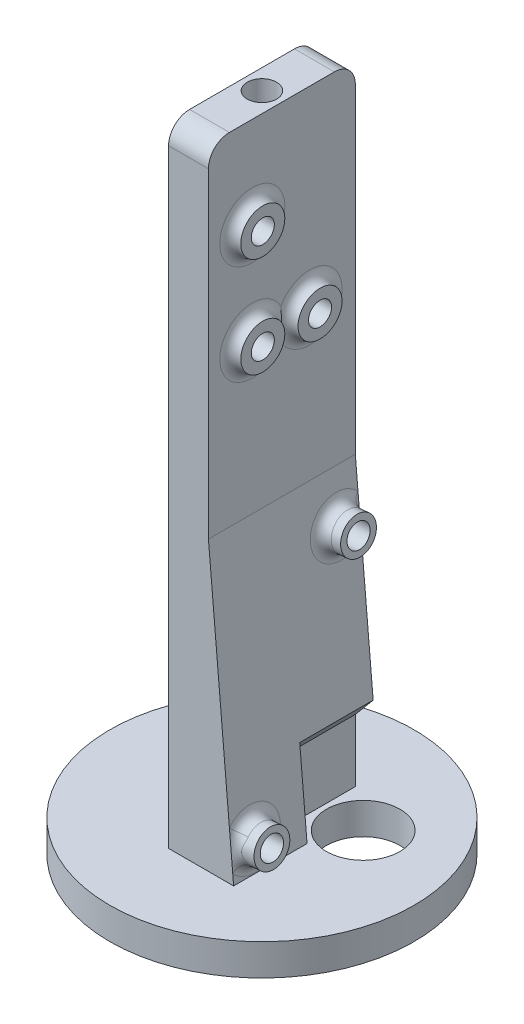
SolidWorks part; units mm, degrees
ref_plane "Front Plane" through (0, 0, 0) normal (0, 0, 1) x (1, 0, 0)
ref_plane "Top Plane" through (0, 0, 0) normal (0, 1, 0) x (1, 0, 0)
ref_plane "Right Plane" through (0, 0, 0) normal (1, 0, 0) x (0, 0, -1)
sketch "Sketch1" plane through (0, 418.4142, 0) normal (0, -1, 0) x (1, 0, 0)
  line L1 (-2.413, -8.89) -> (2.413, -8.89)
  line L2 (-2.413, -8.89) -> (-2.413, 8.89)
  line L3 (-2.413, 8.89) -> (2.413, 8.89)
  line L4 (2.413, -8.89) -> (2.413, 8.89)
  line L5 (-2.413, -8.89) -> (2.413, 8.89) construction
  line L6 (-2.413, 8.89) -> (2.413, -8.89) construction
  point P0 (0, 0)
  dimension "D1" = 4.826
  dimension "D2" = 17.78
extrude "Boss-Extrude1" add sketch "Sketch1" along normal blind 76.2
sketch "Sketch4" plane through (0, 418.4142, 0) normal (0, 1, 0) x (1, 0, 0)
  circle A0 centre (0, 0) radius 1.778
  dimension "D1" = 3.556
extrude "Cut-Extrude2" cut sketch "Sketch4" against normal up to next
sketch "Sketch5" plane through (0, 342.2142, 0) normal (0, -1, 0) x (1, 0, 0)
  circle A0 centre (0, 0) radius 18.415
  circle A1 centre (0, 0) radius 1.778 construction
  circle A2 centre (0, 0) radius 1.778
  dimension "D1" = 36.83
extrude "Boss-Extrude2" add sketch "Sketch5" along normal blind 3.81
sketch "Sketch8" plane through (0, 338.4042, 0) normal (0, -1, 0) x (1, 0, 0)
  line L1 (-5.08, 0) -> (0, 0) construction
  circle A0 centre (-5.08, 0) radius 0.762
  dimension "D2" = 1.524
  dimension "D1" = 5.08
extrude "Cut-Extrude4" cut sketch "Sketch8" against normal up to next
sketch "Sketch10" plane through (2.413, 0, 0) normal (1, 0, 0) x (0, 0, -1)
  circle A0 centre (-3.5814, 407.3144) radius 1.397
  circle A1 centre (-3.5814, 395.2113) radius 1.397
  circle A2 centre (3.3528, 395.2113) radius 1.397
  circle A3 centre (-3.5814, 407.3144) radius 2.667
  circle A4 centre (-3.5814, 395.2113) radius 2.667
  circle A5 centre (3.3528, 395.2113) radius 2.667
  dimension "D1" = 2.794
  dimension "D2" = 1.27
extrude "Boss-Extrude3" add sketch "Sketch10" along normal blind 1.27
sketch "Sketch11" plane through (2.413, 0, 0) normal (1, 0, 0) x (0, 0, -1)
  circle A0 centre (3.3528, 395.2113) radius 1.397 construction
  circle A1 centre (-3.5814, 395.2113) radius 1.397 construction
  circle A2 centre (-3.5814, 407.3144) radius 1.397 construction
  circle A3 centre (3.3528, 395.2113) radius 1.397
  circle A4 centre (-3.5814, 395.2113) radius 1.397
  circle A5 centre (-3.5814, 407.3144) radius 1.397
extrude "Cut-Extrude5" cut sketch "Sketch11" against normal up to surface (4.826 mm away) up to face at (-2.413, 380.3142, 0)
sketch "Sketch12" plane through (0, 0, -8.89) normal (0, 0, -1) x (-1, 0, 0)
  line L0 (-2.413, 342.2142) -> (-5.461, 342.2142)
  line L1 (18.415, 342.2142) -> (-18.415, 342.2142) construction
  line L2 (-5.461, 342.2142) -> (-2.413, 377.053)
  line L3 (-2.413, 342.2142) -> (-2.413, 418.4142) construction
  line L4 (-2.413, 377.053) -> (-2.413, 342.2142)
  dimension "D1" = 5
  dimension "D2" = 3.048
extrude "Boss-Extrude4" add sketch "Sketch12" against normal up to surface (17.78 mm away) up to face at (0, 380.3142, 8.89)
sketch "Sketch7" plane through (0, 338.4042, 0) normal (0, -1, 0) x (1, 0, 0)
  circle A0 centre (7.473, -4.7831) radius 4.445
  dimension "D1" = 8.89
extrude "Cut-Extrude3" cut sketch "Sketch7" against normal up to surface (3.81 mm away) up to face at (0, 342.2142, -18.415)
sketch "Sketch13" plane through (0, 0, -8.89) normal (0, 0, -1) x (-1, 0, 0)
  line L0 (-2.413, 342.2142) -> (-6.223, 342.2142)
  line L1 (2.413, 342.2142) -> (-5.461, 342.2142) construction
  line L2 (18.415, 342.2142) -> (-18.415, 342.2142) construction
  line L3 (-2.413, 342.2142) -> (-2.413, 348.5642)
  line L4 (-2.413, 348.5642) -> (-6.223, 348.5642)
  line L5 (-6.223, 348.5642) -> (-6.223, 342.2142)
  line L6 (-2.413, 377.053) -> (-2.413, 418.4142) construction
  dimension "D1" = 6.35
  dimension "D2" = 3.81
extrude "Cut-Extrude6" cut sketch "Sketch13" against normal blind 8.89
chamfer "Chamfer1" distance 3.81 angle 45 1 edges at (4.9054, 348.5642, -4.445) first distance on face at (4.2598, 355.9438, 0)
sketch "Sketch14" plane through (35.132, 3.0736, 0) normal (0.9962, 0.0872, 0) x (0, 0, -1)
  circle A0 centre (6.35, 369.3708) radius 1.397
  circle A1 centre (-6.35, 343.9708) radius 1.397
  circle A2 centre (-6.35, 343.9708) radius 2.159
  circle A3 centre (6.35, 369.3708) radius 2.159
  dimension "D1" = 2.794
  dimension "D2" = 0.762
extrude "Boss-Extrude5" add sketch "Sketch14" along normal blind 2.413
fillet "Fillet1" radius 1.27 2 edges at (4.9648, 347.8863, 6.35) (2.751, 373.1897, -6.35)
fillet "Fillet2" radius 1.27 3 edges at (2.413, 407.3144, 6.2484) (2.413, 395.2113, -0.6858) (2.413, 395.2113, 6.2484)
fillet "Fillet3" radius 2.54 2 edges at (0, 418.4142, 8.89) (0, 418.4142, -8.89)
